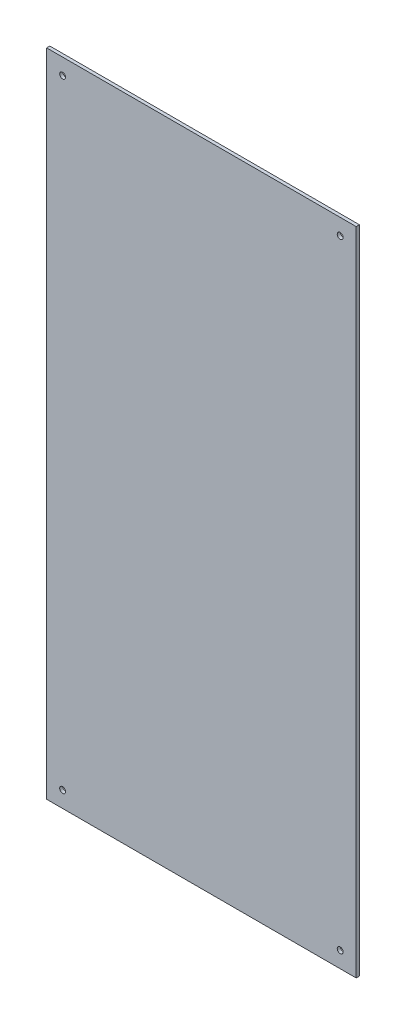
SolidWorks part; units mm, degrees
material "Acrylic (Medium-high impact)"
ref_plane "Front Plane" through (0, 0, 0) normal (0, 0, 1) x (1, 0, 0)
ref_plane "Top Plane" through (0, 0, 0) normal (0, 1, 0) x (1, 0, 0)
ref_plane "Right Plane" through (0, 0, 0) normal (1, 0, 0) x (0, 0, -1)
sketch "Sketch1" plane through (0, 0, 0) normal (0, 0, 1) x (1, 0, 0)
  line L0 (159.5, 0) -> (-159.5, 0) construction
  line L1 (-145, 304.8) -> (145, 304.8)
  line L2 (-145, 304.8) -> (-145, -304.8)
  line L3 (-145, -304.8) -> (145, -304.8)
  line L4 (145, 304.8) -> (145, -304.8)
  line L5 (-145, 304.8) -> (145, -304.8) construction
  line L6 (-145, -304.8) -> (145, 304.8) construction
  point P0 (0, 0)
  point P5 (-129.995, 289.795)
  point P6 (129.995, 289.795)
  point P7 (2, -228.6)
  point P9 (2, -132.6)
  point P10 (95, -132.6)
  point P11 (95, -228.6)
  point P16 (129.995, -289.795)
  point P17 (-129.995, -289.795)
  dimension "D1" = 609.6
  dimension "D2" = 290
  dimension "D3" = 15.005
  dimension "D4" = 15.005
  dimension "D5" = 15.005
  dimension "D6" = 96
  dimension "D7" = 93
  dimension "D8" = 76.2
  dimension "D9" = 50
extrude "Boss-Extrude1" add sketch "Sketch1" along normal blind 3
hole_wizard "M5 Clearance Hole1" positions "Sketch2" profile "Sketch3" hole size "M5" standard "ANSI Metric" end condition through all
sketch "Sketch2" plane through (0, 0, 3) normal (0, 0, 1) x (1, 0, 0)
  point P0 (129.995, 289.795)
  point P3 (-129.995, 289.795)
  point P6 (-129.995, -289.795)
  point P9 (129.995, -289.795)
sketch "Sketch3" plane through (129.995, 289.795, 3) normal (1, 0, 0) x (0, -1, 0)
  line L0 (0, 0) -> (0, 3)
  line L1 (0, 3) -> (2.75, 3)
  line L2 (2.75, 3) -> (2.75, 0)
  line L5 (2.75, 0) -> (0, 0)
  line L11 (0, -6.35) -> (0, 107.95) construction
  dimension "Thru Hole Dia." = 5.5
  dimension "Thru Hole Depth" = 3
